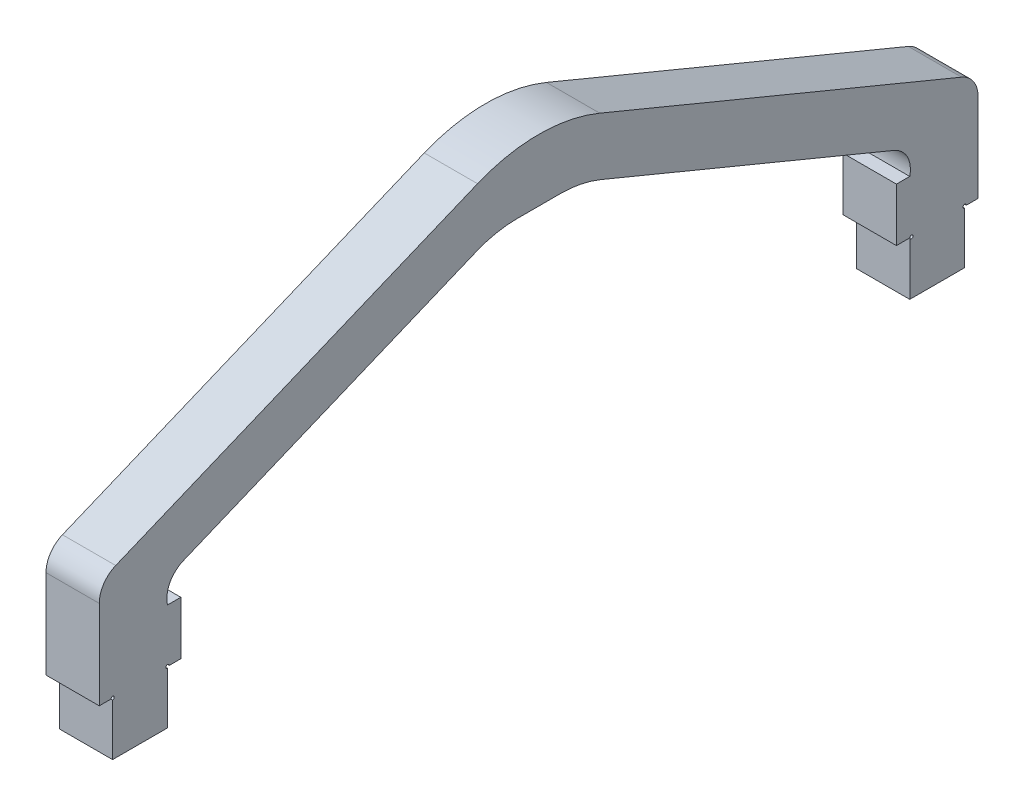
SolidWorks part; units mm, degrees
ref_plane "Front Plane" through (0, 0, 0) normal (0, 0, 1) x (1, 0, 0)
ref_plane "Top Plane" through (0, 0, 0) normal (0, 1, 0) x (1, 0, 0)
ref_plane "Right Plane" through (0, 0, 0) normal (1, 0, 0) x (0, 0, -1)
sketch "Sketch1" plane through (0, 0, 0) normal (1, 0, 0) x (0, 0, -1)
  line L0 (0, 0) -> (0, 25.4) construction
  line L1 (44.25, 0) -> (42.6625, 0) construction
  line L2 (50.8, 0) -> (52.3875, 0)
  line L3 (52.3875, 0) -> (52.3875, 12.7)
  line L4 (-50.8, 0) -> (-50.8, -6.35)
  line L5 (-50.8, -6.35) -> (-44.25, -6.35)
  line L6 (-44.25, 0) -> (-44.25, -6.35)
  line L7 (50.8, 0) -> (50.8, -6.35)
  line L8 (50.8, -6.35) -> (44.25, -6.35)
  line L9 (44.25, 0) -> (44.25, -6.35)
  line L10 (-44.25, 0) -> (-42.6625, 0)
  line L11 (5.0881, 25.4) -> (-5.0881, 25.4)
  line L13 (6.35, 31.75) -> (52.3875, 12.7)
  line L14 (-44.25, 6.35) -> (-42.6625, 6.35)
  line L15 (5.0881, 25.4) -> (46.0375, 8.4554)
  line L16 (44.25, 6.35) -> (46.0375, 8.4554)
  line L17 (3.9221, 25.8825) -> (46.0375, 8.4554) construction
  line L19 (46.0375, 0) -> (46.0375, 8.4554) construction
  line L20 (-6.35, 31.75) -> (-52.3875, 12.7)
  line L21 (-52.3875, 0) -> (-52.3875, 12.7)
  line L22 (-44.25, 6.35) -> (-46.0375, 8.4554)
  line L23 (-5.0881, 25.4) -> (-46.0375, 8.4554)
  line L24 (-50.8, 0) -> (-52.3875, 0)
  line L25 (-42.6625, 0) -> (-42.6625, 6.35)
  line L26 (42.6625, 0) -> (42.6625, 6.35)
  line L27 (42.6625, 6.35) -> (44.25, 6.35)
  line L28 (42.6625, 0) -> (44.25, 0)
  line L29 (-44.25, 6.35) -> (44.25, 6.35) construction
  line L30 (0, 0) -> (-44.25, 0) construction
  line L31 (-44.25, 0) -> (44.25, 0) construction
  line L32 (-6.35, 31.75) -> (0, 34.3776)
  line L33 (6.35, 31.75) -> (0, 34.3776)
  point P6 (0, 0)
  point P15 (-6.35, 25.4)
  point P16 (6.35, 25.4)
  point P17 (0, 25.4)
  dimension "D1" = 25.4
  dimension "D2" = 101.6
  dimension "D3" = 6.35
  dimension "D4" = 6.55
  dimension "D5" = 1.5875
  dimension "D6" = 6.35
  dimension "D8" = 12.7
  dimension "D10" = 1.5875
  dimension "D9" = 6.35
extrude "Boss-Extrude1" add sketch "Sketch1" along normal blind 6.35 contours L24 L4 L5 L6 L10 L9 L8 L7 L2 L3 L13 L20 L21 L23 L11 L15 L16 L14 L22 region at (0, -3.175, -49.6759)
sketch "Sketch2" plane through (6.35, 0, 0) normal (1, 0, 0) x (0, 0, -1)
  circle A0 centre (-50.8, 0) radius 0.1984
  circle A1 centre (-44.25, 0) radius 0.1984
  circle A2 centre (44.45, 0) radius 0.1984
  circle A3 centre (50.8, 0) radius 0.1984
  dimension "D1" = 0.3969
  dimension "D2" = 0.3969
extrude "Cut-Extrude1" cut sketch "Sketch2" against normal through all
fillet "Fillet5" radius 3.175 4 edges at (3.175, 8.4554, 46.0375) (3.175, 8.4554, -46.0375) (3.175, 12.7, -52.3875) (3.175, 12.7, 52.3875)
fillet "Fillet6" radius 12.7 2 edges at (3.175, 25.4, 5.0881) (3.175, 25.4, -5.0881)
fillet "Fillet7" radius 19.05 1 edges at (3.175, 34.3776, 0)
